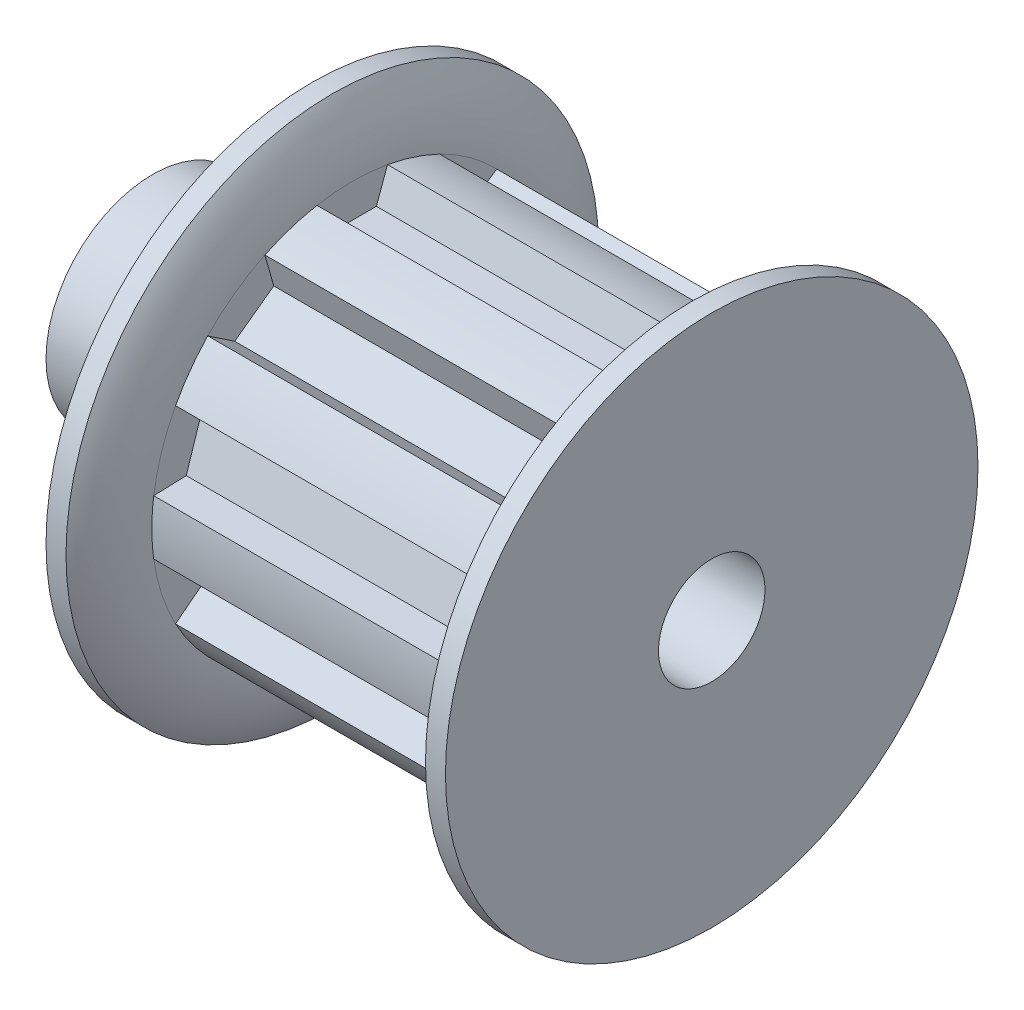
SolidWorks part; units mm, degrees
ref_plane "Front Plane" through (0, 0, 0) normal (0, 0, 1) x (1, 0, 0)
ref_plane "Top Plane" through (0, 0, 0) normal (0, 1, 0) x (1, 0, 0)
ref_plane "Right Plane" through (0, 0, 0) normal (1, 0, 0) x (0, 0, -1)
sketch "Sketch2" plane through (0, 0, 0) normal (1, 0, 0) x (0, 0, -1)
  line L3 (0, 0) -> (0, 6.325) construction
  line L6 (0, 6.325) -> (0, 7.525) construction
  line L7 (-1.325, 7.4074) -> (-0.9072, 6.2596)
  line L8 (1.325, 7.4074) -> (0.9072, 6.2596)
  line L9 (0, -2.2) -> (0, -3.2) construction
  line L10 (0, 8.025) -> (0, 7.525) construction
  line L12 (-0.9072, 6.2596) -> (0.9072, 6.2596)
  line L15 (0, 0) -> (0, -2.2) construction
  circle A0 centre (0, 0) radius 8.025 construction
  circle A1 centre (0, 0) radius 6.325 construction
  arc A7 (1.325, 7.4074) -> (-1.325, 7.4074) centre (0, 0) ccw
  dimension "D1" = 40
  dimension "D3" = 0.5
  dimension "D2" = 1.2
  dimension "D4" = 2.65
sketch "Sketch1" plane through (0, 0, 0) normal (0, 0, 1) x (1, 0, 0)
  line L0 (-10.5, 0) -> (10.5, 0) construction
  line L1 (-10.5, 2) -> (10.5, 2)
  line L2 (-10.5, 2) -> (-10.5, 4)
  line L3 (-4.5, 10) -> (-3.75, 10)
  line L4 (-3, 7.525) -> (-4.5, 7.525) construction
  line L5 (9.75, 7.525) -> (9.75, 10) construction
  line L6 (-3, 7.525) -> (9, 7.525)
  line L8 (9, 7.525) -> (10.5, 7.525) construction
  line L9 (9.75, 10) -> (10.5, 10)
  line L10 (10.5, 10) -> (10.5, 2)
  line L12 (-7.5, 4) -> (-7.5, 2) construction
  line L13 (-4.5, 10) -> (-4.5, 4)
  line L14 (-4.5, 4) -> (-10.5, 4)
  arc A0 (9, 7.525) -> (9.75, 10) centre (13.4588, 7.525) cw
  arc A1 (-3, 7.525) -> (-3.75, 10) centre (-7.4588, 7.525) ccw
  dimension "Bore Size" = 4
  dimension "Overall Width" = 21
  dimension "Inside Width" = 12
  dimension "Outside Width" = 15
  dimension "Hub Dia" = 8
  dimension "OD" = 20
revolve "Revolve1" add sketch "Sketch1" angle 360 mid plane about L0
sketch "Sketch3" plane through (0, 0, 0) normal (1, 0, 0) x (0, 0, -1)
  line L2 (-1.325, 7.4074) -> (-0.9072, 6.2596) construction
  line L3 (-0.9072, 6.2596) -> (0.9072, 6.2596) construction
  line L4 (1.325, 7.4074) -> (0.9072, 6.2596) construction
  line L5 (-1.325, 7.4074) -> (-0.9072, 6.2596)
  line L6 (-0.9072, 6.2596) -> (0.9072, 6.2596)
  line L7 (1.325, 7.4074) -> (0.9072, 6.2596)
  arc A1 (1.325, 7.4074) -> (-1.325, 7.4074) centre (0, 0) ccw construction
  arc A2 (1.325, 7.4074) -> (-1.325, 7.4074) centre (0, 0) ccw
extrude "Cut-Extrude1" cut sketch "Sketch3" along normal up to vertex (9 mm away) from vertex up to point (9, 7.525, 0) starting at point (-3, 7.525, 0)
pattern_circular "CirPattern1" count 10 over 360 of "Cut-Extrude1"
sketch "Sketch5" plane through (0, 0, 0) normal (0, 0, 1) x (1, 0, 0)
  line L0 (9, 6.7716) -> (9, 5.2139) construction
  point P0 (9, 0)
equation "\"D3@Sketch2\" = \"ht@Sketch2\"/2"
equation "\"D2@Sketch2\" = \"hs@Sketch2\"-\"ht@Sketch2\""
